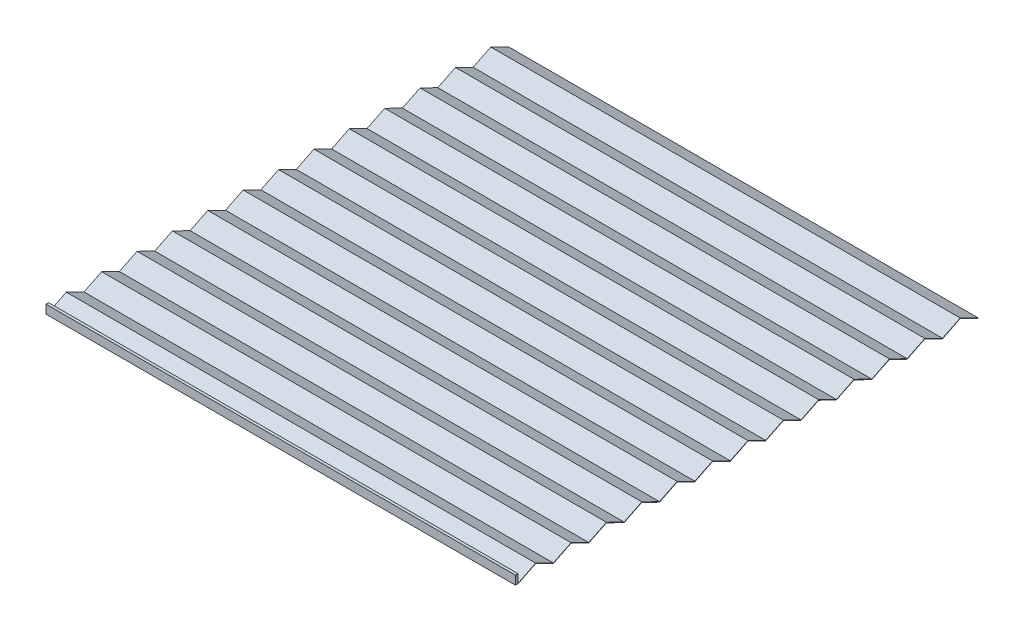
SolidWorks part; units mm, degrees
ref_plane "Front Plane" through (0, 0, 0) normal (0, 0, 1) x (1, 0, 0)
ref_plane "Top Plane" through (0, 0, 0) normal (0, 1, 0) x (1, 0, 0)
ref_plane "Right Plane" through (0, 0, 0) normal (1, 0, 0) x (0, 0, -1)
sketch "Sketch2" plane through (0, 0, 0) normal (0, 0, 1) x (1, 0, 0)
  line L1 (-270, 10) -> (270, 10)
  line L2 (-270, 10) -> (-270, 0)
  line L3 (-270, 0) -> (270, 0)
  line L4 (270, 10) -> (270, 0)
  point P4 (0, 0)
  dimension "D1" = 10
  dimension "D2" = 540
extrude "Boss-Extrude1" add sketch "Sketch2" along normal blind 3
sketch "Sketch3" plane through (270, 0, 0) normal (1, 0, 0) x (0, 0, -1)
  line L0 (0, 10) -> (529.1401, 10) construction
  line L1 (0, 0) -> (529.1401, 0) construction
  line L2 (529.1401, 10) -> (529.1401, 0) construction
  line L3 (0, 0) -> (20.3515, 10)
  line L4 (20.3515, 10) -> (40.7031, 0)
  line L5 (40.7031, 0) -> (61.0546, 10)
  line L6 (61.0546, 10) -> (81.4062, 0)
  line L7 (81.4062, 0) -> (101.7577, 10)
  line L8 (101.7577, 10) -> (122.1093, 0)
  line L9 (122.1093, 0) -> (142.4608, 10)
  line L10 (142.4608, 10) -> (162.8123, 0)
  line L11 (162.8123, 0) -> (183.1639, 10)
  line L12 (183.1639, 10) -> (203.5154, 0)
  line L13 (203.5154, 0) -> (223.867, 10)
  line L14 (223.867, 10) -> (244.2185, 0)
  line L15 (244.2185, 0) -> (264.5701, 10)
  line L16 (264.5701, 10) -> (284.9216, 0)
  line L17 (284.9216, 0) -> (305.2731, 10)
  line L18 (305.2731, 10) -> (325.6247, 0)
  line L20 (325.6247, 0) -> (345.9762, 10)
  line L21 (345.9762, 10) -> (366.3278, 0)
  line L22 (366.3278, 0) -> (386.6793, 10)
  line L23 (386.6793, 10) -> (407.0309, 0)
  line L24 (407.0309, 0) -> (427.3824, 10)
  line L25 (427.3824, 10) -> (447.7339, 0)
  line L26 (447.7339, 0) -> (468.0855, 10)
  line L27 (468.0855, 10) -> (488.437, 0)
  line L28 (488.437, 0) -> (508.7886, 10)
  line L29 (508.7886, 10) -> (529.1401, 0)
  line L30 (529.1401, 10) -> (529.1401, 0) construction
extrude "Extrude-Thin1" add sketch "Sketch3" against normal through all thin thin type mid plane wall 0.5
